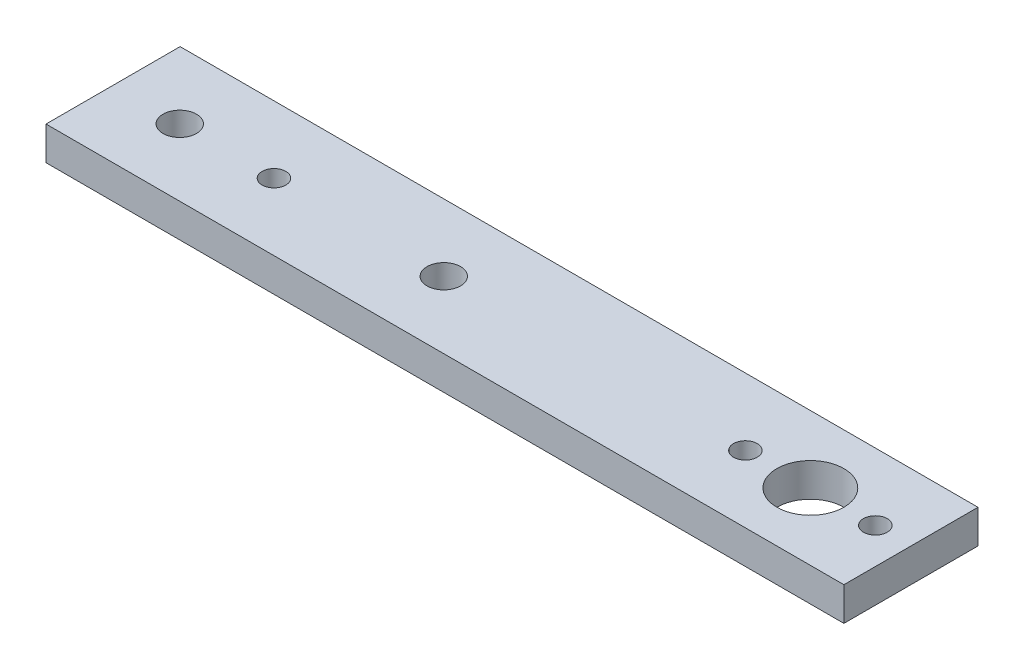
SolidWorks part; units mm, degrees
ref_plane "Front Plane" through (0, 0, 0) normal (0, 0, 1) x (1, 0, 0)
ref_plane "Top Plane" through (0, 0, 0) normal (0, 1, 0) x (1, 0, 0)
ref_plane "Right Plane" through (0, 0, 0) normal (1, 0, 0) x (0, 0, -1)
sketch "Sketch1" plane through (0, 0, 0) normal (0, 1, 0) x (1, 0, 0)
  line L1 (-34.925, 12.7) -> (34.925, 12.7)
  line L2 (-34.925, 12.7) -> (-34.925, -12.7)
  line L3 (-34.925, -12.7) -> (34.925, -12.7)
  line L4 (34.925, 12.7) -> (34.925, -12.7)
  line L5 (-34.925, 12.7) -> (34.925, -12.7) construction
  line L6 (-34.925, -12.7) -> (34.925, 12.7) construction
  circle A0 centre (15.875, 0) radius 6.35
  point P0 (0, 0)
  dimension "D3" = 12.7
  dimension "D1" = 25.4
  dimension "D2" = 50.8
  dimension "D4" = 19.05
extrude "Boss-Extrude1" add sketch "Sketch1" along normal blind 6.35
sketch "Sketch3" plane through (0, 0, 0) normal (0, -1, 0) x (1, 0, 0)
  line L0 (34.925, -12.7) -> (-34.925, -12.7) construction
  line L1 (-34.925, 12.7) -> (-116.205, 12.7)
  line L2 (-34.925, 12.7) -> (-34.925, -12.7)
  line L3 (-34.925, -12.7) -> (-116.205, -12.7)
  line L4 (-116.205, 12.7) -> (-116.205, -12.7)
  dimension "D1" = 81.28
extrude "Boss-Extrude2" add sketch "Sketch3" against normal up to surface (6.35 mm away) up to face at (0, 6.35, 0)
sketch "Sketch4" plane through (0, 0, 0) normal (0, -1, 0) x (1, 0, 0)
  line L12 (34.925, -12.7) -> (34.925, 12.7)
  line L13 (34.925, 12.7) -> (-116.205, 12.7)
  line L14 (-116.205, 12.7) -> (-116.205, -12.7)
  line L15 (-116.205, -12.7) -> (34.925, -12.7)
  line L16 (34.925, -12.7) -> (34.925, 12.7)
  line L17 (34.925, 12.7) -> (-116.205, 12.7)
  line L18 (-116.205, 12.7) -> (-116.205, -12.7)
  line L19 (-116.205, -12.7) -> (34.925, -12.7)
  circle A0 centre (-53.5599, 0) radius 3.175 construction
  circle A1 centre (-53.5599, 0) radius 3.175
  circle A2 centre (-85.725, 0) radius 1.7272 construction
  circle A3 centre (-85.725, 0) radius 1.7272 construction
  circle A4 centre (-85.725, 0) radius 2.2479
  circle A5 centre (-103.5686, 0) radius 3.175
  ellipse E0 centre (-103.5686, 0) end of major axis (-103.5686, -3.175) minor radius 3.1739 construction
  point P22 (-103.5686, 0)
  dimension "D1" = 4.4958
  dimension "D3" = 6.35
  dimension "D2" = 0
extrude "Cut-Extrude2" cut sketch "Sketch4" against normal through all contours A1 | A4 | A5 region at (-53.5599, 0, 0)
sketch "Sketch5" plane through (0, 0, 0) normal (0, -1, 0) x (1, 0, 0)
  circle A0 centre (28.1813, 0) radius 2.2479 construction
  circle A1 centre (3.5687, 0) radius 2.2479 construction
  circle A2 centre (28.1813, 0) radius 2.2479
  circle A3 centre (3.5687, 0) radius 2.2479
extrude "Cut-Extrude3" cut sketch "Sketch5" against normal through all
